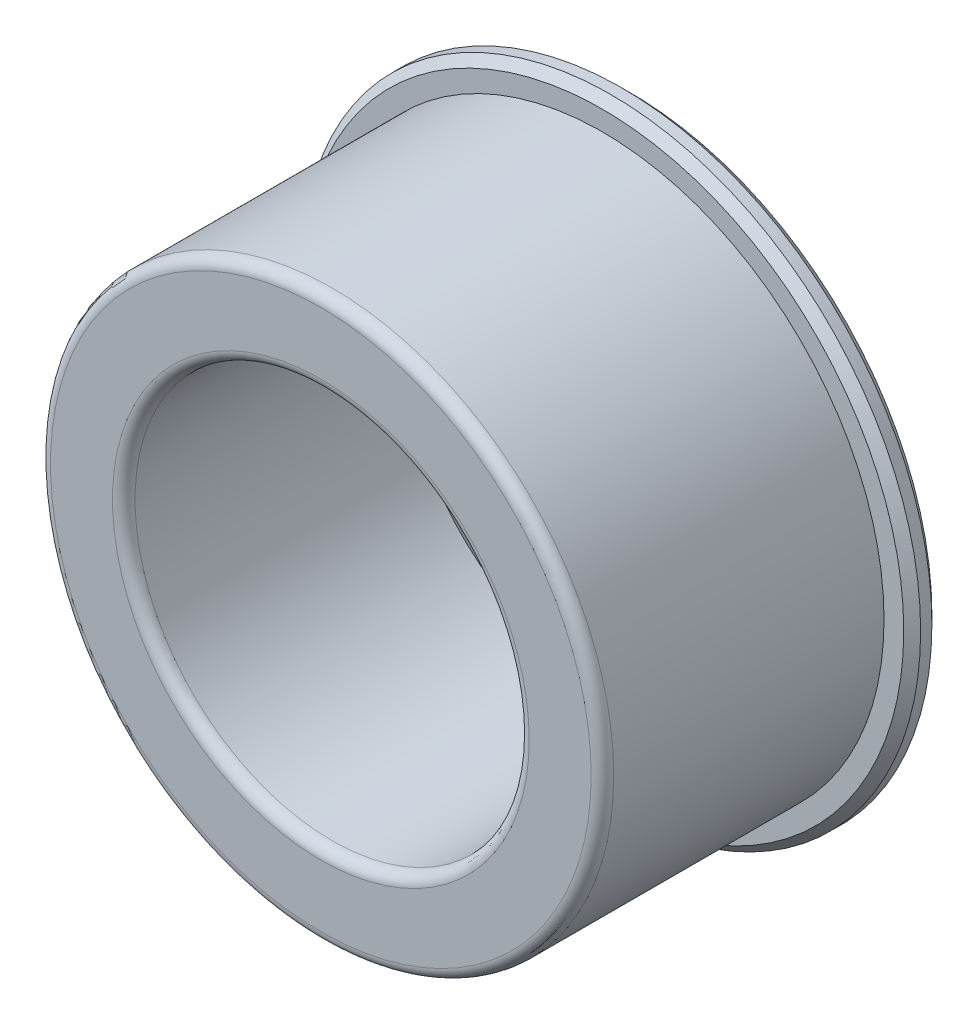
SolidWorks part; units mm, degrees
ref_plane "Front Plane" through (0, 0, 0) normal (0, 0, 1) x (1, 0, 0)
ref_plane "Top Plane" through (0, 0, 0) normal (0, 1, 0) x (1, 0, 0)
ref_plane "Right Plane" through (0, 0, 0) normal (1, 0, 0) x (0, 0, -1)
sketch "Sketch2" plane through (0, 0, 0) normal (0, 0, 1) x (1, 0, 0)
  circle A0 centre (0, 0) radius 10
  circle A1 centre (0, 0) radius 7
  circle A2 centre (0, 0) radius 11
  dimension "D1" = 20
  dimension "D3" = 1
  dimension "D2" = 3
extrude "Boss-Extrude1" add sketch "Sketch2" along normal blind 10 contours A0 A1 region at (-9.7172, 0, 0)
extrude "Boss-Extrude2" add sketch "Sketch2<3>" against normal blind 1 contours A2 A0 | A0 A1 region at (-9.7172, 0, 0) region at (-10.6889, 0, 0)
sketch "Sketch2<3>" plane through (0, 0, 0) normal (0, 0, 1) x (1, 0, 0) same geometry as "Sketch2"
chamfer "Chamfer1" distance 0.3 angle 45 1 edges at (11, 0, 0)
chamfer "Chamfer2" distance 0.3 angle 45 1 edges at (11, 0, -1)
chamfer "Chamfer3" distance 1 angle 45 1 edges at (7, 0, -1)
fillet "Fillet1" radius 0.4 2 edges at (7, 0, 10) (10, 0, 10)
